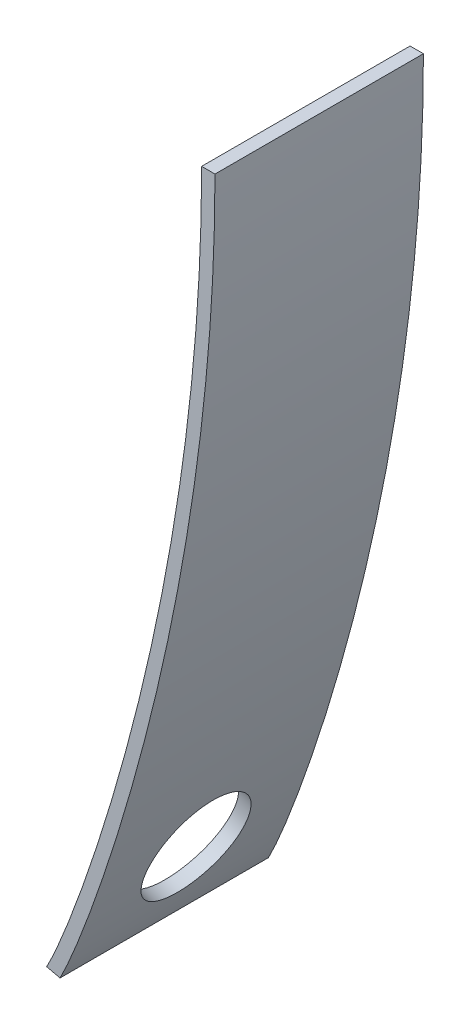
SolidWorks part; units mm, degrees
ref_plane "Front Plane" through (0, 0, 0) normal (0, 0, 1) x (1, 0, 0)
ref_plane "Top Plane" through (0, 0, 0) normal (0, 1, 0) x (1, 0, 0)
ref_plane "Right Plane" through (0, 0, 0) normal (1, 0, 0) x (0, 0, -1)
sketch "Sketch1" plane through (0, 0, 0) normal (0, 0, 1) x (1, 0, 0)
  line L0 (0, 29.3553) -> (0, 0) construction
  line L1 (0, 0) -> (-9.5996, -25.4183) construction
  line L2 (-9.5996, -25.4183) -> (-11.8001, -29.5747) construction
  line L3 (-1.016, 29.3553) -> (0, 29.3553)
  line L5 (-11.8001, -29.5747) -> (-12.8239, -29.337)
  line L6 (-12.8239, -29.337) -> (-12.6981, -29.0994)
  spline S0 degree 3 poles (0, 29.3553) (0, 0) (-9.5996, -25.4183) (-11.8001, -29.5747) knots 0 0 0 0 1 1 1 1
  spline S1 degree 1 poles (-1.016, 29.3553) (-12.6981, -29.0994) knots 0 0 1 1 construction
  spline S2 degree 3 poles (-1.016, 29.3553) (-1.016, 27.5503) (-1.0904, 23.9152) (-1.5043, 16.8554) (-2.457, 8.3615) (-4.0994, -1.0565) (-6.0427, -9.5056) (-7.7471, -15.5658) (-9.0619, -19.7231) (-9.9986, -22.4696) (-10.8605, -24.8184) (-11.4952, -26.4219) (-11.9393, -27.4773) (-12.2372, -28.1519) (-12.4511, -28.6092) (-12.6023, -28.9153) (-12.6643, -29.0356) (-12.6981, -29.0994) knots 0 0 0 0 0.0625 0.125 0.25 0.375 0.5 0.625 0.6875 0.75 0.8125 0.875 0.90625 0.9375 0.96875 0.984375 1 1 1 1
  dimension "D1" = 1.016
extrude "Boss-Extrude1" add sketch "Sketch1" along normal blind 15.875
sketch3d "3DSketch1"
  point P0 (-10.5897, -24.0711, 8.0106)
ref_plane "Plane1" through (-9.6372, -24.4248, 8.0106) normal (0.9374, -0.3481, 0) x (0, 0, -1)
ref_plane "Plane2" through (0, 0, 7.9375) normal (0, 0, 1) x (1, 0, 0)
ref_plane "Plane3" through (-5.3237, -22.9298, 0) normal (-0.2262, -0.9741, 0) x (-0.9741, 0.2262, 0)
sketch "Sketch4" plane through (-5.3237, -22.9298, 0) normal (-0.2262, -0.9741, 0) x (-0.9741, 0.2262, 0)
  point P0 (-2.3932, -7.9375)
  point P1 (0, 0)
sketch "Sketch3" plane through (-9.6372, -24.4248, 8.0106) normal (0.9374, -0.3481, 0) x (0, 0, -1)
  line L2 (-7.8644, -5.5808) -> (8.0106, -5.5808) construction
  line L3 (0.0731, 33.3051) -> (0.0731, 19.1988) construction
  circle A0 centre (0.0731, 0.7692) radius 3.9688
  point P0 (0.0731, 0.7692)
  point P4 (0, 0)
  point P5 (0, 0)
  point P8 (0, 0)
  point P9 (0, 0)
  dimension "D1" = 7.9375
  dimension "D2" = 6.35
extrude "Cut-Extrude1" cut sketch "Sketch3" against normal through all
